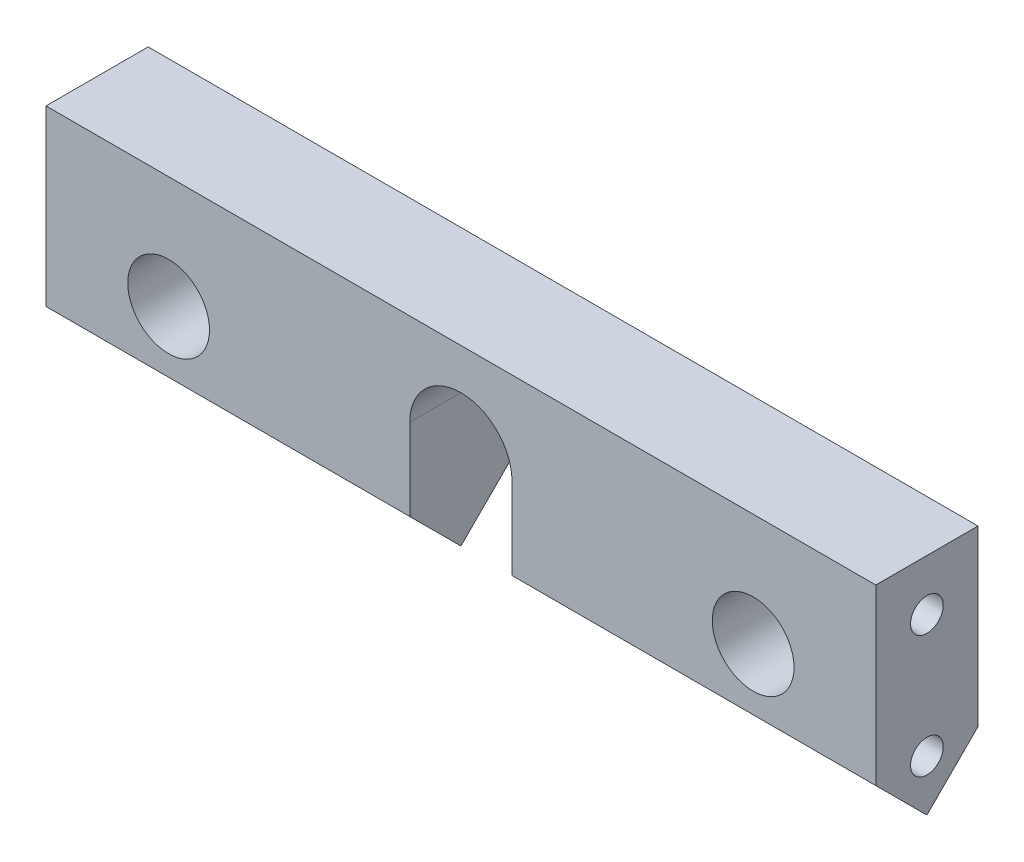
SolidWorks part; units mm, degrees
ref_plane "Front Plane" through (0, 0, 0) normal (0, 0, 1) x (1, 0, 0)
ref_plane "Top Plane" through (0, 0, 0) normal (0, 1, 0) x (1, 0, 0)
ref_plane "Right Plane" through (0, 0, 0) normal (1, 0, 0) x (0, 0, -1)
sketch "Sketch1" plane through (0, 0, 0) normal (1, 0, 0) x (0, 0, -1)
  line L0 (0, 0) -> (-2.5, 2.5)
  line L1 (-2.5, 2.5) -> (-2.5, 11)
  line L2 (-2.5, 11) -> (2.5, 11)
  line L3 (2.5, 11) -> (2.5, 2.5)
  line L4 (2.5, 2.5) -> (0, 0)
  dimension "D1" = 5
  dimension "D2" = 8.5
extrude "Boss-Extrude1" add sketch "Sketch1" along normal blind 40.6
hole_wizard "Tap Drill for M2x0.4 Tap1" positions "Sketch3" profile "Sketch2" hole size "M2x0.4" standard "ANSI Metric"
sketch "Sketch3" plane through (40.6, 0, 0) normal (1, 0, 0) x (0, 0, -1)
  point P0 (0, 8.5)
  point P2 (0, 2.5)
  dimension "D1" = 6
  dimension "D2" = 2.5
sketch "Sketch2" plane through (40.6, 8.5, 0) normal (0, 1, 0) x (0, 0, -1)
  line L0 (0, 0) -> (0, 5.4807)
  line L1 (0, 5.4807) -> (0.8, 5)
  line L2 (0.8, 5) -> (0.8, 0)
  line L5 (0.8, 0) -> (0, 0)
  line L10 (0, 5.4807) -> (-0.8, 5) construction
  line L11 (0, -6.35) -> (0, 107.95) construction
  dimension "Hole Dia." = 1.6
  dimension "Hole Depth" = 5
  dimension "Drill Angle" = 118
hole_wizard "Tap Drill for M2x0.4 Tap2" positions "Sketch5" profile "Sketch4" hole size "M2x0.4" standard "ANSI Metric"
sketch "Sketch5" plane through (0, 0, 0) normal (-1, 0, 0) x (0, 0, 1)
  point P0 (0, 8.5)
  point P2 (0, 2.5)
  dimension "D1" = 2.5
  dimension "D2" = 6
sketch "Sketch4" plane through (0, 8.5, 0) normal (0, 1, 0) x (0, 0, 1)
  line L0 (0, 0) -> (0, 5.4807)
  line L1 (0, 5.4807) -> (0.8, 5)
  line L2 (0.8, 5) -> (0.8, 0)
  line L5 (0.8, 0) -> (0, 0)
  line L10 (0, 5.4807) -> (-0.8, 5) construction
  line L11 (0, -6.35) -> (0, 107.95) construction
  dimension "Hole Dia." = 1.6
  dimension "Hole Depth" = 5
  dimension "Drill Angle" = 118
hole_wizard "Tap Drill for M2x0.4 Tap3" positions "Sketch7" profile "Sketch6" hole size "M2x0.4" standard "ANSI Metric" end condition up to next
sketch "Sketch7" plane through (0, 0, 0) normal (0, -0.7071, 0.7071) x (-1, 0, 0)
  line L0 (0, -3.5355) -> (0, 0) construction
  line L1 (-40.6, -3.5355) -> (-40.6, 0) construction
  line L2 (-40.6, 0) -> (0, 0) construction
  point P0 (-10.3, -1.8)
  point P2 (-30.3, -1.8)
  dimension "D1" = 10.3
  dimension "D2" = 10.3
  dimension "D3" = 1.8
sketch "Sketch6" plane through (10.3, 1.2728, 1.2728) normal (1, 0, 0) x (0, -0.7071, -0.7071)
  line L0 (0, 0) -> (0, 5.3355)
  line L1 (0, 5.3355) -> (0.8, 5.3355)
  line L2 (0.8, 5.3355) -> (0.8, 0)
  line L5 (0.8, 0) -> (0, 0)
  line L11 (0, -6.35) -> (0, 107.95) construction
  dimension "Thru Hole Dia." = 1.6
  dimension "Thru Hole Depth" = 5.3355
sketch "Sketch8" plane through (0, 0, 2.5) normal (0, 0, 1) x (1, 0, 0)
  line L0 (17.8, 0) -> (17.8, 6.5)
  line L1 (40.6, 0) -> (0, 0) construction
  line L2 (22.8, 6.5) -> (22.8, 0)
  line L3 (22.8, 0) -> (17.8, 0)
  line L4 (0, 2.5) -> (0, 0) construction
  line L5 (0, 11) -> (0, 2.5) construction
  line L6 (40.6, 11) -> (0, 11) construction
  line L7 (40.6, 11) -> (40.6, 2.5) construction
  circle A0 centre (6, 5.5) radius 2
  circle A1 centre (34.6, 5.5) radius 2
  arc A2 (17.8, 6.5) -> (22.8, 6.5) centre (20.3, 6.5) cw
  dimension "D1" = 4
  dimension "D2" = 2.5
  dimension "D3" = 17.8
  dimension "D4" = 6
  dimension "D5" = 5.5
  dimension "D6" = 6
  dimension "D7" = 4.5
extrude "Cut-Extrude1" cut sketch "Sketch8" against normal up to next
